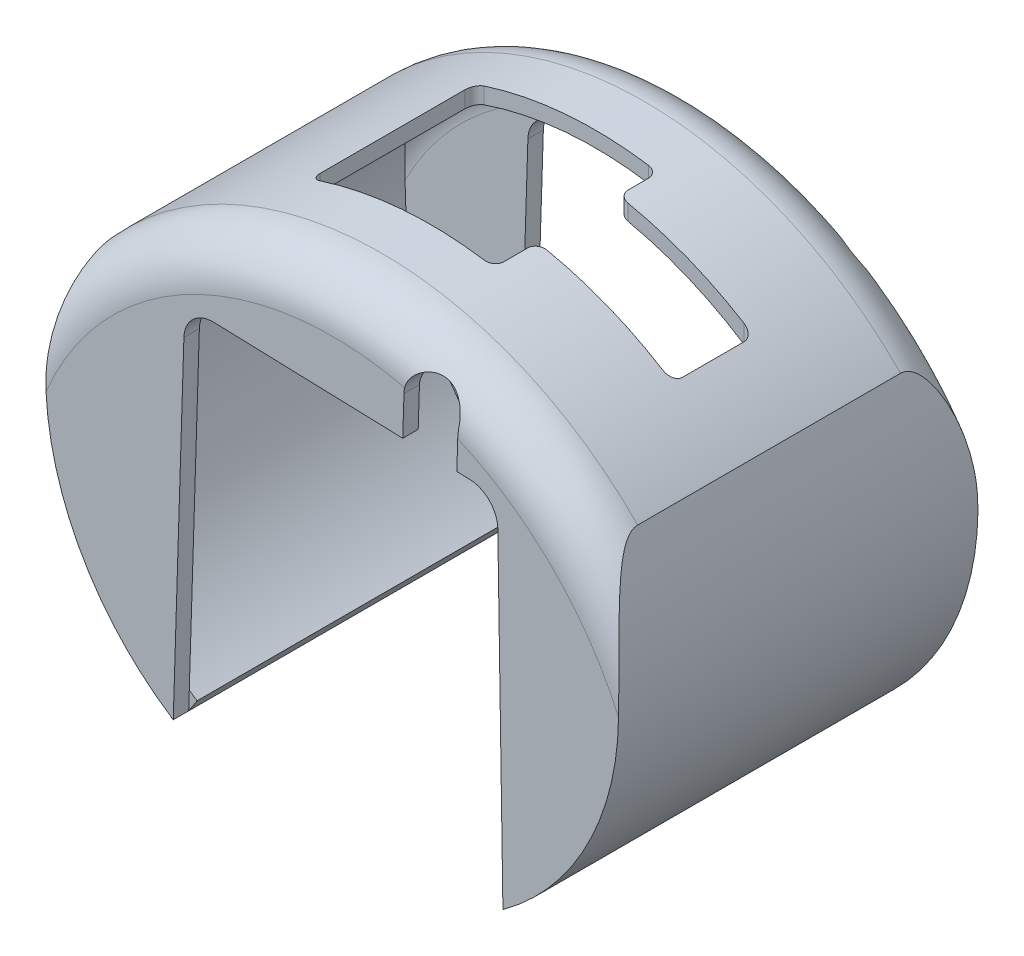
SolidWorks part; units mm, degrees
ref_plane "Front Plane" through (0, 0, 0) normal (0, 0, 1) x (1, 0, 0)
ref_plane "Top Plane" through (0, 0, 0) normal (0, 1, 0) x (1, 0, 0)
ref_plane "Right Plane" through (0, 0, 0) normal (1, 0, 0) x (0, 0, -1)
sketch "Sketch1" plane through (0, 0, 0) normal (0, 0, 1) x (1, 0, 0)
  line L0 (-7.7853, -24.2772) -> (-8.2208, -24.9483)
  line L1 (8.368, -24.2772) -> (8.8392, -24.9236)
  line L2 (2.1212, -6.5391) -> (-1.0766, -6.5391) construction
  line L10 (-7.0281, -6.5391) -> (-7.0281, -4.5182) construction
  line L11 (-3.5194, -4.5182) -> (-7.0281, -4.5182) construction
  line L12 (-3.5194, -6.5391) -> (-3.5194, -4.5182) construction
  line L13 (-3.5194, -6.5391) -> (-7.0281, -6.5391) construction
  line L14 (-1.0766, -6.5391) -> (-1.0766, -2.4974) construction
  line L15 (2.1212, -2.4974) -> (-1.0766, -2.4974) construction
  line L16 (2.1212, -6.5391) -> (2.1212, -2.4974) construction
  arc A0 (-8.2208, -24.9483) -> (-13.7161, -7.2378) centre (-0.3347, -12.7936) cw
  arc A1 (13.3152, -6.7006) -> (-13.7161, -7.2378) centre (0.0535, -19.7463) ccw
  arc A2 (8.8392, -24.9236) -> (13.3152, -6.7006) centre (0.2597, -13.1551) ccw
  arc A9 (12.6542, -7.1701) -> (-13.0297, -7.6729) centre (0.0535, -19.7463) ccw
  arc A10 (-7.7853, -24.2772) -> (-13.0297, -7.6729) centre (-0.3347, -12.7936) cw
  arc A11 (8.368, -24.2772) -> (12.6542, -7.1701) centre (0.2597, -13.1551) ccw
  dimension "D1" = 0.8
extrude "Boss-Extrude1" add sketch "Sketch1" along normal blind 17
sketch "Sketch2" plane through (0, 0, 0) normal (0, 1, 0) x (1, 0, 0)
  line L0 (3.3546, -7.5989) -> (10.3546, -7.5989) construction
  line L1 (-5.6791, -4.2512) -> (2.8209, -4.2512)
  line L2 (-6.1791, -4.7512) -> (-6.1791, -12.2488)
  line L3 (-5.6791, -12.7488) -> (2.8209, -12.7488)
  line L4 (3.3209, -12.2488) -> (3.3209, -11)
  line L5 (3.8209, -10.5) -> (9.8209, -10.5)
  line L6 (3.8209, -6.3) -> (9.8209, -6.3)
  line L7 (10.3209, -6.8) -> (10.3209, -10)
  line L8 (3.3209, -4.7512) -> (3.3209, -5.8)
  line L15 (-0.2004, -17) -> (-0.2004, 0) construction
  line L16 (-0.2004, -17) -> (-0.2004, -8.5) construction
  line L17 (-0.2004, -8.5) -> (-7.1969, -8.5) construction
  arc A0 (10.3209, -6.8) -> (9.8209, -6.3) centre (9.8209, -6.8) ccw
  arc A1 (10.3209, -10) -> (9.8209, -10.5) centre (9.8209, -10) cw
  arc A2 (3.8209, -6.3) -> (3.3209, -5.8) centre (3.8209, -5.8) cw
  arc A3 (3.8209, -10.5) -> (3.3209, -11) centre (3.8209, -11) ccw
  arc A4 (2.8209, -4.2512) -> (3.3209, -4.7512) centre (2.8209, -4.7512) cw
  arc A5 (2.8209, -12.7488) -> (3.3209, -12.2488) centre (2.8209, -12.2488) ccw
  arc A6 (-6.1791, -4.7512) -> (-5.6791, -4.2512) centre (-5.6791, -4.7512) cw
  arc A7 (-6.1791, -12.2488) -> (-5.6791, -12.7488) centre (-5.6791, -12.2488) ccw
  dimension "D3" = 0.5
extrude "Cut-Extrude1" cut sketch "Sketch2" against normal blind 10
sketch "Sketch3" plane through (0, 0, 17) normal (0, 0, 1) x (1, 0, 0)
  line L0 (-7.6209, -6.0365) -> (8.5529, -6.5495)
  line L1 (-8.2208, -24.9483) -> (-7.6209, -6.0365)
  line L2 (-13.7161, -7.2378) -> (-12.3547, -5.8863)
  line L3 (8.8392, -24.9236) -> (8.5529, -6.5495)
  arc A0 (13.3152, -6.7006) -> (-13.7161, -7.2378) centre (0.0535, -19.7463) ccw construction
  arc A1 (13.3152, -6.7006) -> (-12.3547, -5.8863) centre (0.0535, -19.7463) ccw
  arc A2 (-13.7161, -7.2378) -> (-8.2208, -24.9483) centre (-0.3347, -12.7936) ccw construction
  arc A3 (-13.7161, -7.2378) -> (-8.2208, -24.9483) centre (-0.3347, -12.7936) ccw
  arc A5 (8.8392, -24.9236) -> (13.3152, -6.7006) centre (0.2597, -13.1551) ccw construction
  arc A6 (8.8392, -24.9236) -> (13.3152, -6.7006) centre (0.2597, -13.1551) ccw
extrude "Boss-Extrude2" add sketch "Sketch3" along normal blind 0.8
fillet "Fillet1" radius 2.5 1 edges at (0.6433, -1.1529, 17.8)
sketch "Sketch4" plane through (0, 0, 0) normal (0, 0, -1) x (-1, 0, 0)
  line L3 (7.6209, -6.0365) -> (8.2208, -24.9483)
  line L4 (-8.8392, -24.9236) -> (-8.5529, -6.5495)
  line L5 (-8.5529, -6.5495) -> (7.6209, -6.0365)
  arc A0 (-13.3152, -6.7006) -> (-8.8392, -24.9236) centre (-0.2597, -13.1551) ccw construction
  arc A1 (8.2208, -24.9483) -> (13.7161, -7.2378) centre (0.3347, -12.7936) ccw construction
  arc A2 (13.7161, -7.2378) -> (-13.3152, -6.7006) centre (-0.0535, -19.7463) ccw construction
  arc A3 (-13.3152, -6.7006) -> (-8.8392, -24.9236) centre (-0.2597, -13.1551) ccw
  arc A4 (8.2208, -24.9483) -> (13.7161, -7.2378) centre (0.3347, -12.7936) ccw
  arc A5 (13.7161, -7.2378) -> (-13.3152, -6.7006) centre (-0.0535, -19.7463) ccw
extrude "Boss-Extrude3" add sketch "Sketch4" along normal blind 0.8
fillet "Fillet2" radius 2.5 1 edges at (-0.3162, -1.1472, -0.8)
fillet "Fillet3" radius 1.5 4 edges at (-7.6209, -6.0365, 17.4) (8.5529, -6.5495, 17.4) (8.5529, -6.5495, -0.4) (-7.6209, -6.0365, -0.4)
sketch "Sketch5" plane through (0, 0, 17.8) normal (0, 0, 1) x (1, 0, 0)
  line L0 (5.0544, -6.4385) -> (5.1193, -4.3927) construction
  line L1 (-6.1216, -6.084) -> (7.1229, -6.5041) construction
  line L2 (3.6551, -6.3941) -> (3.72, -4.3483)
  line L3 (6.4537, -6.4829) -> (6.5186, -4.4371)
  arc A0 (3.6551, -6.3941) -> (6.4537, -6.4829) centre (5.0544, -6.4385) ccw
  arc A1 (6.5186, -4.4371) -> (3.72, -4.3483) centre (5.1193, -4.3927) ccw
  point P4 (5.0869, -5.4156)
extrude "Cut-Extrude2" cut sketch "Sketch5" against normal blind 0.8
sketch "Sketch6" plane through (0, 0, -0.8) normal (0, 0, -1) x (-1, 0, 0)
  line L0 (-6.9677, -5.4865) -> (-6.9677, -6.8865)
  line L2 (-8.5219, -6.8779) -> (-8.5752, -7.98)
  line L3 (-8.5752, -7.98) -> (-6.9677, -7.98)
  line L4 (-6.9677, -7.98) -> (-6.9677, -6.8865)
  arc A0 (-8.5219, -6.8779) -> (-6.9677, -5.4865) centre (-8.3677, -5.4865) cw
extrude "Cut-Extrude3" cut sketch "Sketch6" against normal blind 1
fillet "Fillet5" radius 2 2 edges at (-0.2949, -1.9469, 17) (-2.8577, -2.1832, 0)
